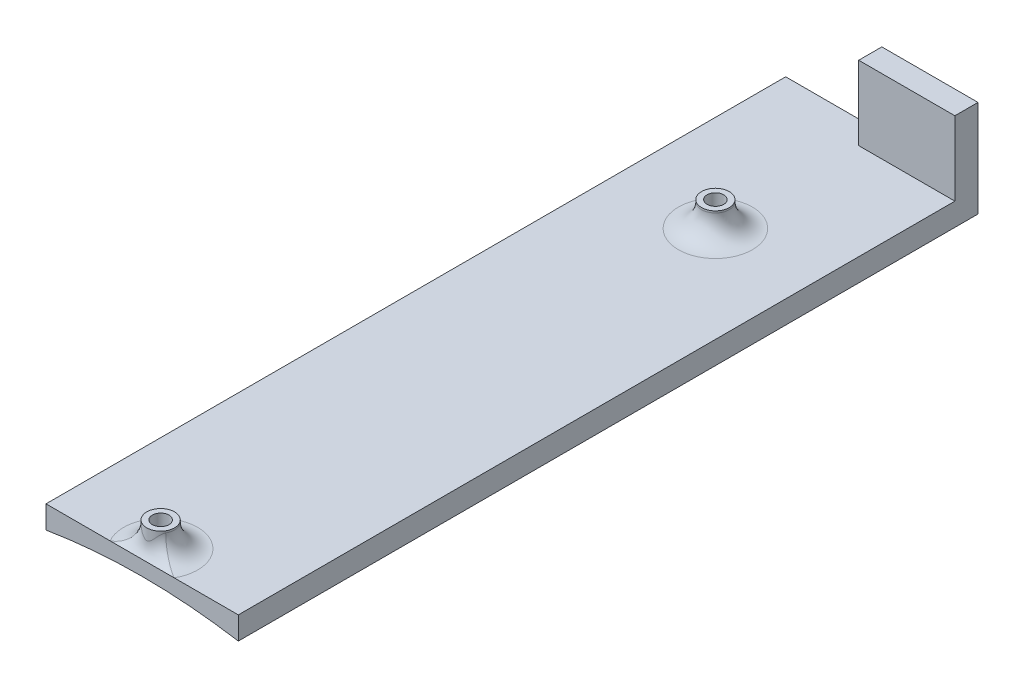
SolidWorks part; units mm, degrees
ref_plane "Front Plane" through (0, 0, 0) normal (0, 0, 1) x (1, 0, 0)
ref_plane "Top Plane" through (0, 0, 0) normal (0, 1, 0) x (1, 0, 0)
ref_plane "Right Plane" through (0, 0, 0) normal (1, 0, 0) x (0, 0, -1)
sketch "Sketch3" plane through (0, 0, 0) normal (0, 0, 1) x (1, 0, 0)
  line L0 (-13.208, -3.81) -> (13.208, -3.81)
  line L3 (-13.208, -6.9327) -> (-13.208, -3.81)
  line L4 (13.208, -6.9327) -> (13.208, -3.81)
  line L5 (0, -3.81) -> (0, -5.842) construction
  arc A2 (13.208, -6.9327) -> (-13.208, -6.9327) centre (0, -86.36) ccw
  circle A3 centre (0, 0) radius 15.24 construction
  dimension "D1" = 2.032
  dimension "D2" = 26.416
  dimension "D3" = 161.036
  dimension "D4" = 30.48
  dimension "D5" = 3.81
extrude "Boss-Extrude1" add sketch "Sketch3" along normal blind 101.6
sketch "Sketch4" plane through (0, -3.81, 0) normal (0, 1, 0) x (1, 0, 0)
  line L1 (13.208, -101.6) -> (-13.208, -101.6) construction
  circle A0 centre (0, -22.86) radius 1.143
  circle A1 centre (0, -99.06) radius 1.143
  circle A2 centre (0, -22.86) radius 1.905
  circle A3 centre (0, -99.06) radius 1.905
  dimension "D1" = 76.2
  dimension "D2" = 2.286
  dimension "D3" = 2.54
  dimension "D4" = 3.81
  dimension "D5" = 3.81
extrude "Boss-Extrude2" add sketch "Sketch4" along normal blind 3.429
fillet "Fillet1" radius 3.175 2 edges at (1.905, -3.81, 22.86) (1.905, -3.81, 99.06)
sketch "Sketch5" plane through (0, -3.81, 0) normal (0, 1, 0) x (1, 0, 0)
  line L0 (13.208, -101.6) -> (13.208, 0) construction
  line L1 (-13.208, 0) -> (13.208, 0)
  line L2 (-13.208, 0) -> (-13.208, -3.175)
  line L3 (-13.208, -3.175) -> (13.208, -3.175)
  line L4 (13.208, 0) -> (13.208, -3.175)
  dimension "D1" = 3.175
extrude "Boss-Extrude3" add sketch "Sketch5" along normal blind 10.16
sketch "Sketch8" plane through (0, 0, 0) normal (0, 0, -1) x (-1, 0, 0)
  line L5 (0, 6.35) -> (0, -5.842)
  line L12 (13.208, -6.9327) -> (13.208, 6.35)
  line L13 (13.208, 6.35) -> (-13.208, 6.35)
  line L14 (-13.208, 6.35) -> (-13.208, -6.9327)
  line L15 (13.208, -6.9327) -> (13.208, 6.35)
  line L16 (13.208, 6.35) -> (-13.208, 6.35)
  line L17 (-13.208, 6.35) -> (-13.208, -6.9327)
  arc A1 (13.208, -6.9327) -> (-13.208, -6.9327) centre (0, -86.36) ccw
  arc A2 (13.208, -6.9327) -> (-13.208, -6.9327) centre (0, -86.36) ccw
  point P0 (0, 0)
  point P7 (0, -7.1083)
  point P9 (-12.7, -6.8499)
  line M5 (13.208, -6.9327) -> (13.208, 6.35)
  line M6 (13.208, 6.35) -> (-13.208, 6.35)
  arc M8 (-13.208, -6.9327) -> (13.208, -6.9327) centre (0, -86.36) cw
  dimension "D1" = 0
extrude "Cut-Extrude1" cut sketch "Sketch8" against normal up to surface (3.175 mm away) contours L5 M6 M8 M5 region at (-6.6995, 0.0685, 0) up to face at (0, 1.27, 3.175)
sketch "Sketch9" plane through (0, 0, 3.175) normal (0, 0, -1) x (-1, 0, 0)
  line L3 (13.208, -3.81) -> (0, -3.81)
  line L4 (0, -3.81) -> (0, -5.842)
  line L5 (0, -3.81) -> (0, -5.842)
  line L6 (13.208, -3.81) -> (0, -3.81)
  line L9 (13.208, -6.9327) -> (13.208, -3.81)
  line L10 (13.208, -6.9327) -> (13.208, -3.81)
  arc A1 (13.208, -6.9327) -> (0, -5.842) centre (0, -86.36) ccw
  arc A2 (13.208, -6.9327) -> (0, -5.842) centre (0, -86.36) ccw
  dimension "D1" = 0
extrude "Boss-Extrude4" add sketch "Sketch9" along normal blind 3.175
